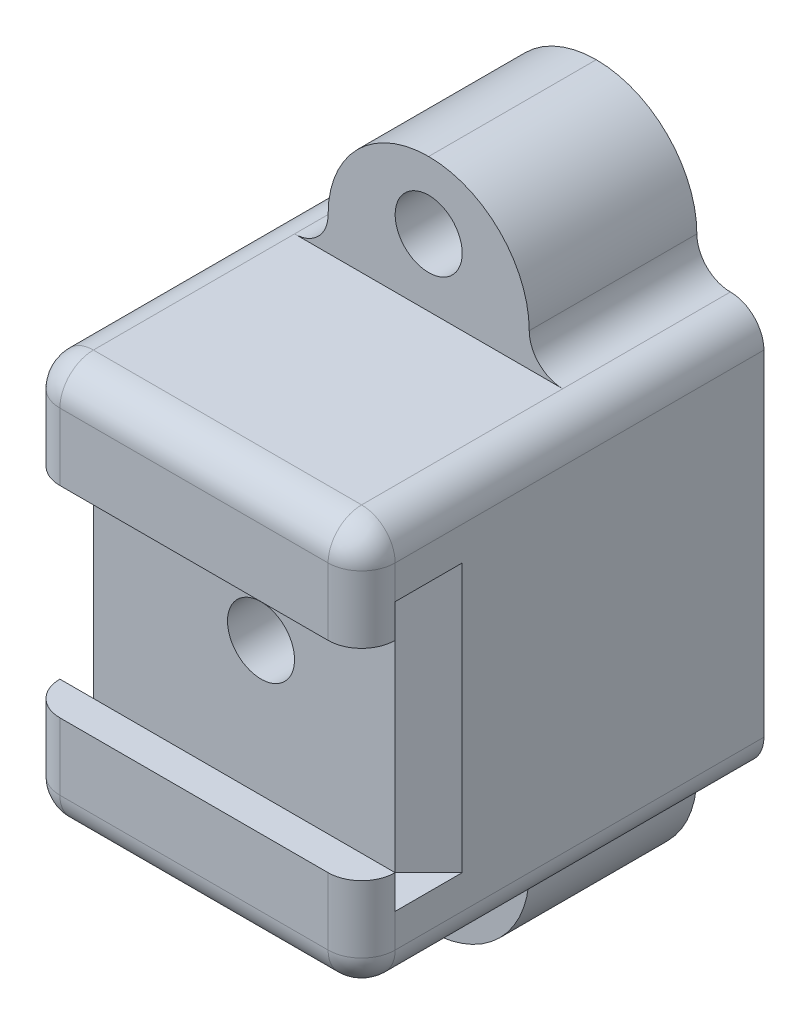
SolidWorks part; units mm, degrees
ref_plane "Front Plane" through (0, 0, 0) normal (0, 0, 1) x (1, 0, 0)
ref_plane "Top Plane" through (0, 0, 0) normal (0, 1, 0) x (1, 0, 0)
ref_plane "Right Plane" through (0, 0, 0) normal (1, 0, 0) x (0, 0, -1)
sketch "Sketch2" plane through (0, 0, 0) normal (0, 0, 1) x (1, 0, 0)
  line L1 (0, -1) -> (10, -1)
  line L2 (0, -1) -> (0, 11)
  line L3 (0, 11) -> (10, 11)
  line L4 (10, -1) -> (10, 11)
  point P5 (0, 0)
  point P6 (0, 0)
extrude "Boss-Extrude1" add sketch "Sketch2" along normal blind 15 contours L1 L4 L3 L2
sketch "Sketch5" plane through (0, 0, 0) normal (0, 0, -1) x (-1, 0, 0)
  circle A0 centre (-5, 5) radius 3.2
extrude "Cut-Extrude1" cut sketch "Sketch5" against normal blind 8.5 contours A0
sketch "Sketch6" plane through (0, 0, 8.5) normal (0, 0, -1) x (-1, 0, 0)
  circle A0 centre (-5, 5) radius 1
extrude "Cut-Extrude2" cut sketch "Sketch6" against normal blind 2.5 contours A0
sketch "Sketch8" plane through (10, 0, 0) normal (1, 0, 0) x (0, 0, -1)
  line L2 (-11, 5) -> (-11, 1)
  line L4 (-11, 5) -> (-11, 9)
  line L5 (-11, 9) -> (-10, 9)
  line L6 (-10, 5) -> (-10, 9)
  line L7 (-11, 1) -> (-10, 1)
  line L8 (-10, 5) -> (-10, 1)
extrude "Cut-Extrude3" cut sketch "Sketch8" against normal through all both and the other way through all contours L4 L5 L6 L8 L7 L2
sketch "Sketch11" plane through (0, 0, 11) normal (0, 0, -1) x (-1, 0, 0)
  circle A0 centre (-5, 5) radius 1
extrude "Cut-Extrude4" cut sketch "Sketch11" against normal blind 1.5
chamfer "Chamfer1" distance 1 angle 45 1 edges at (10, 5, 10)
fillet "Fillet3" radius 1 4 edges at (5, -1, 15) (0, 5, 15) (5, 11, 15) (10, 5, 15)
fillet "Fillet4" radius 1 8 edges at (0.2929, 10.7071, 14.7071) (0.2929, -0.7071, 14.7071) (9.7071, -0.7071, 14.7071) (9.7071, 10.7071, 14.7071) (0, 11, 7) (0, -1, 7) (10, -1, 7) (10, 11, 7)
sketch "Sketch21" plane through (0, 11, 0) normal (0, 1, 0) x (1, 0, 0)
  line L0 (1, 0) -> (9, 0) construction
  line L1 (5, 0) -> (2, 0)
  line L3 (5, -5) -> (2, -5)
  line L4 (2, 0) -> (2, -5)
  line L6 (5, 0) -> (8, 0)
  line L8 (5, -5) -> (8, -5)
  line L9 (8, 0) -> (8, -5)
extrude "Boss-Extrude6" add sketch "Sketch21" along normal blind 4
sketch "Sketch22" plane through (0, 0, 5) normal (0, 0, 1) x (1, 0, 0)
  circle A0 centre (5, 13) radius 1
extrude "Cut-Extrude10" cut sketch "Sketch22" against normal through all both and the other way through all
fillet "Fillet12" radius 3 2 edges at (2, 15, 2.5) (8, 15, 2.5)
sketch "Sketch23" plane through (0, 0, 0) normal (0, 0, -1) x (-1, 0, 0)
  line L0 (0, 0) -> (0, 10) construction
  line L1 (-5, 1.8) -> (0, 1.8)
  line L2 (-5, 1.8) -> (-5, 7.55)
  line L4 (0, 1.8) -> (0, 7.55)
  line L5 (-5, 7.55) -> (-5, 8.2)
  line L6 (-5, 8.2) -> (0, 8.2)
  line L7 (0, 8.2) -> (0, 7.55)
  circle A0 centre (-5, 5) radius 3.2 construction
  circle A1 centre (-5, 5) radius 3.2 construction
extrude "Cut-Extrude12" cut sketch "Sketch23" against normal blind 1
pattern_circular "CirPattern7" count 2 over 360 about axis through (5, 5, 8.5) along (0, 0, -1) of "Boss-Extrude6", "Cut-Extrude10"
fillet "Fillet16" radius 3 2 edges at (8, -5, 2.5) (2, -5, 2.5)
fillet "Fillet17" radius 1 2 edges at (8, -1, 2.5) (2, -1, 2.5)
fillet "Fillet18" radius 1 2 edges at (2, 11, 2.5) (8, 11, 2.5)
sketch "Sketch24" plane through (0, 0, 0) normal (-1, 0, 0) x (0, 0, 1)
  line L3 (12, 11.791) -> (15.7157, 11.791)
  line L4 (15.7157, 11.791) -> (15.7157, -1.5768)
  line L5 (15.7157, -1.5768) -> (12, -1.5768)
  line L8 (11, 9) -> (11, 1) construction
  line L9 (11, 4.0788) -> (11, 6)
  line L10 (12, 10) -> (12, 8)
  line L11 (14, 10) -> (0, 10) construction
  line L12 (12, 10) -> (12, 11.791)
  line L13 (12, 8) -> (11, 8)
  line L14 (11, 8) -> (11, 6)
  line L15 (12, 0) -> (12, 2)
  line L16 (0, 0) -> (14, 0) construction
  line L17 (12, -1.5768) -> (12, 0)
  line L18 (12, 2) -> (11, 2)
  line L19 (11, 2) -> (11, 4.0788)
extrude "Cut-Extrude13" cut sketch "Sketch24" against normal blind 10
fillet "Fillet20" radius 1 5 edges at (10, 9, 12) (9.7071, 10.7071, 12) (5, 11, 12) (0.2929, 10.7071, 12) (0, 9, 12)
fillet "Fillet21" radius 1 5 edges at (10, 1, 12) (9.7071, -0.7071, 12) (5, -1, 12) (0.2929, -0.7071, 12) (0, 1, 12)
